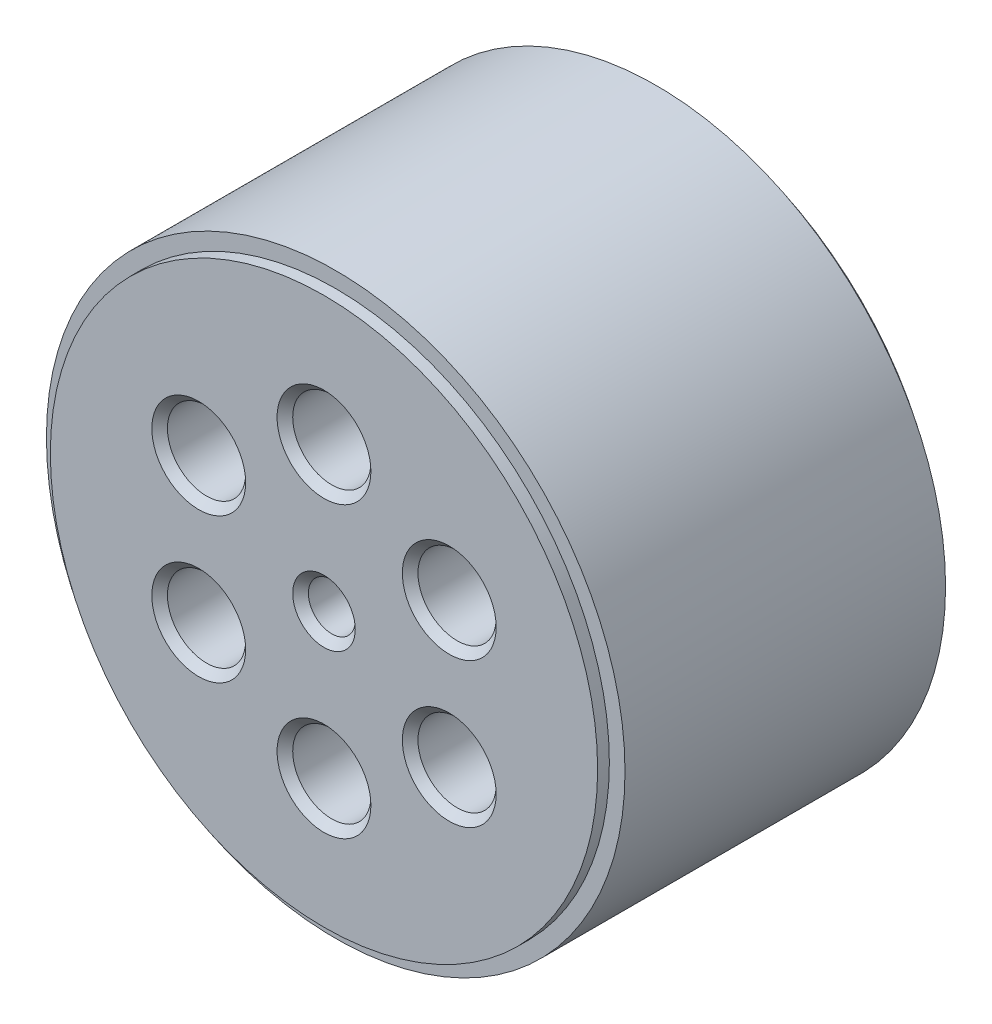
SolidWorks part; units mm, degrees
ref_plane "Plan de face" through (0, 0, 0) normal (0, 0, 1) x (1, 0, 0)
ref_plane "Plan de dessus" through (0, 0, 0) normal (0, 1, 0) x (1, 0, 0)
ref_plane "Plan de droite" through (0, 0, 0) normal (1, 0, 0) x (0, 0, -1)
sketch "Esquisse1" plane through (0, 0, 0) normal (0, 0, 1) x (1, 0, 0)
  line L0 (-3, 0) -> (-18.5, 0) construction
  line L1 (-18.5, 0) -> (-34, 0) construction
  circle A0 centre (0, 0) radius 34
  circle A1 centre (0, 0) radius 3
  circle A2 centre (0, 0) radius 18.5 construction
  circle A3 centre (0, 18.5) radius 5
  circle A4 centre (16.0215, 9.25) radius 5
  circle A5 centre (16.0215, -9.25) radius 5
  circle A6 centre (0, -18.5) radius 5
  circle A7 centre (-16.0215, -9.25) radius 5
  circle A8 centre (-16.0215, 9.25) radius 5
  point P22 (0, 0)
  dimension "D1" = 68
  dimension "D2" = 6
  dimension "D3" = 10
  dimension "D4" = 6
extrude "Boss.-Extru.1" add sketch "Esquisse1" along normal mid plane 44
sketch "Esquisse2" plane through (0, 0, 22) normal (0, 0, 1) x (1, 0, 0)
  circle A0 centre (0, 0) radius 37
  circle A1 centre (0, 0) radius 34
  circle A2 centre (0, 0) radius 34 construction
  dimension "D1" = 74
extrude "Boss.-Extru.2" add sketch "Esquisse2" against normal up to surface (44 mm away) up to face at (34, 0, -22)
extrude "Enlèv. mat.-Extru.1" cut sketch "Esquisse2<3>" against normal blind 1.5
sketch "Esquisse2<3>" plane through (0, 0, 22) normal (0, 0, 1) x (1, 0, 0) same geometry as "Esquisse2"
mirror "Symétrie1" about plane through (0, 0, 0) normal (0, 0, 1) of "Enlèv. mat.-Extru.1"
sketch "Esquisse3" plane through (0, 0, 22) normal (0, 0, 1) x (1, 0, 0)
  circle A1 centre (0, 0) radius 34
  circle A2 centre (0, 0) radius 34 construction
  circle A3 centre (0, 0) radius 35
  dimension "D1" = 1
extrude "Boss.-Extru.3" add sketch "Esquisse3" against normal up to surface (1.5 mm away) up to face at (34, 0, 20.5)
mirror "Symétrie2" about plane through (0, 0, 0) normal (0, 0, 1) of "Boss.-Extru.3"
chamfer "Chanfrein1" distance 1 angle 45 14 edges at (5, -18.5, -22) (5, -18.5, 22) (-11.0215, -9.25, -22) (-11.0215, -9.25, 22) (-11.0215, 9.25, -22) (-11.0215, 9.25, 22) (3, 0, -22) (3, 0, 22) (21.0215, -9.25, -22) (21.0215, -9.25, 22) (21.0215, 9.25, -22) (21.0215, 9.25, 22) (5, 18.5, -22) (5, 18.5, 22)
sketch "Esquisse4" plane through (0, 0, -22) normal (0, 0, -1) x (-1, 0, 0)
  circle A0 centre (0, 0) radius 29
  circle A1 centre (0, 0) radius 35 construction
  dimension "D1" = 6
extrude "Enlèv. mat.-Extru.2" cut sketch "Esquisse4" against normal blind 32
